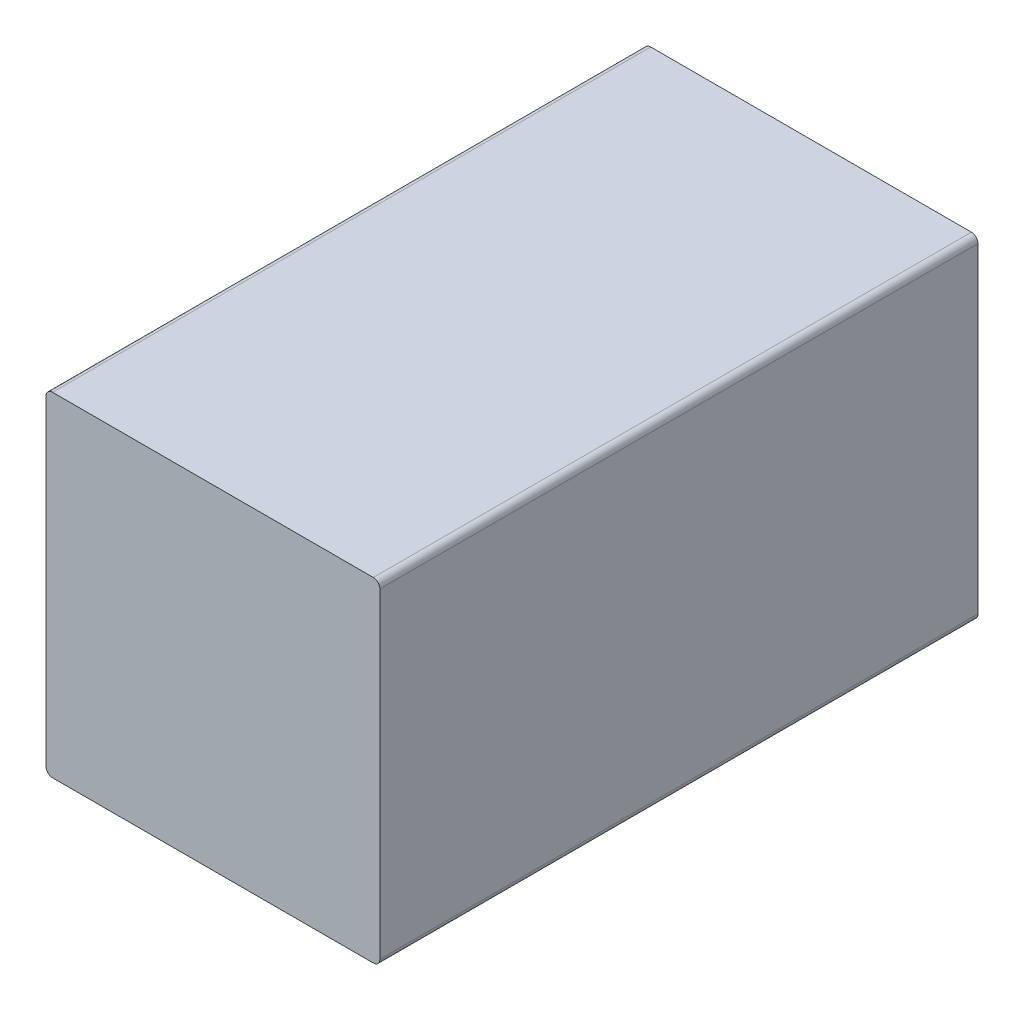
SolidWorks part; units mm, degrees
ref_plane "Front Plane" through (0, 0, 0) normal (0, 0, 1) x (1, 0, 0)
ref_plane "Top Plane" through (0, 0, 0) normal (0, 1, 0) x (1, 0, 0)
ref_plane "Right Plane" through (0, 0, 0) normal (1, 0, 0) x (0, 0, -1)
sketch "Sketch1" plane through (0, 0, 0) normal (0, 0, 1) x (1, 0, 0)
  line L0 (2, 48.8) -> (48.8, 48.8)
  line L1 (0, 0) -> (50.8, 0)
  line L2 (0, 0) -> (0, 50.8)
  line L3 (0, 50.8) -> (50.8, 50.8)
  line L4 (50.8, 0) -> (50.8, 50.8)
  line L5 (48.8, 2) -> (48.8, 48.8)
  line L6 (2, 2) -> (48.8, 2)
  line L7 (4.9083, 69.7541) -> (9.6278, 69.7541)
  line L8 (4.9083, 69.7541) -> (4.9083, 66.1673)
  line L9 (4.9083, 66.1673) -> (9.6278, 66.1673)
  line L10 (9.6278, 69.7541) -> (9.6278, 66.1673)
  line L11 (2, 2) -> (2, 48.8)
  dimension "D1" = 50.8
  dimension "D2" = 2
extrude "Boss-Extrude1" add sketch "Sketch1" along normal blind 1 contours L11 L6 L5 L0 | L1 L4 L3 L2 L6 L11 L0 L5 region at (25.4, 25.4, 0) region at (0.7184, 25.4, 0)
extrude "Boss-Extrude2" add sketch "Sketch1<3>" against normal blind 90 contours L1 L4 L3 L2 L6 L11 L0 L5 region at (0.7184, 25.4, 0)
sketch "Sketch1<3>" plane through (0, 0, 0) normal (0, 0, 1) x (1, 0, 0) same geometry as "Sketch1"
fillet "Fillet1" radius 1 4 edges at (0, 50.8, -44.5) (50.8, 50.8, -44.5) (50.8, 0, -44.5) (0, 0, -44.5)
